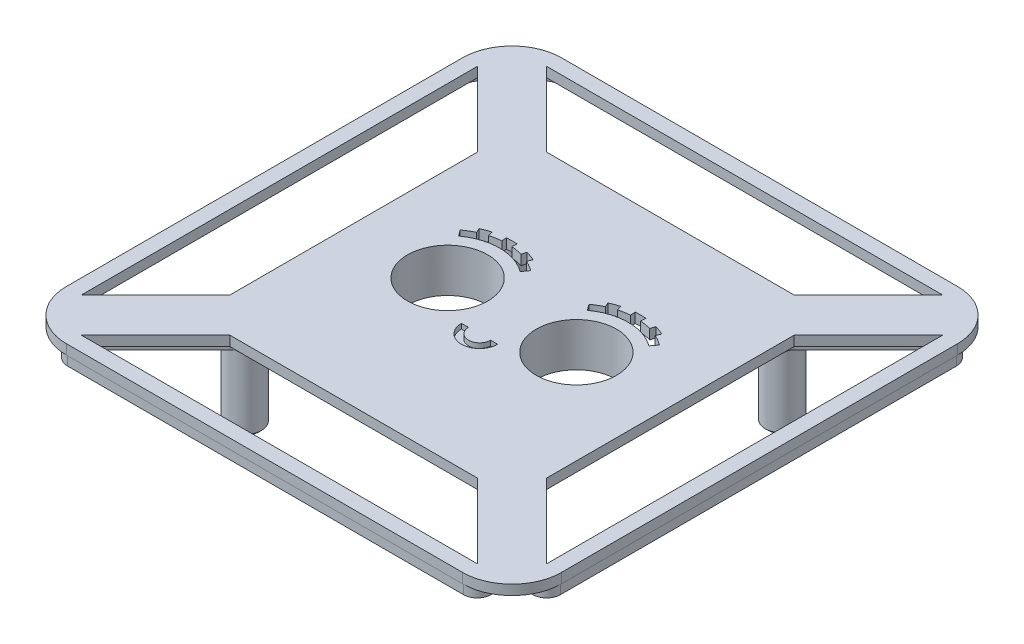
SolidWorks part; units mm, degrees
ref_plane "Front Plane" through (0, 0, 0) normal (0, 0, 1) x (1, 0, 0)
ref_plane "Top Plane" through (0, 0, 0) normal (0, 1, 0) x (1, 0, 0)
ref_plane "Right Plane" through (0, 0, 0) normal (1, 0, 0) x (0, 0, -1)
sketch "Sketch1" plane through (0, 0, 0) normal (0, 1, 0) x (1, 0, 0)
  line L0 (0, 50) -> (3, 50)
  line L1 (10, 0) -> (90, 0)
  line L2 (0, 10) -> (0, 90)
  line L3 (10, 100) -> (90, 100)
  line L4 (100, 10) -> (100, 90)
  line L5 (3, 10) -> (3, 90)
  line L6 (3, 90) -> (18, 75)
  line L7 (18, 75) -> (18, 25)
  line L8 (3, 10) -> (18, 25)
  line L9 (50, 82) -> (50, 18) construction
  line L10 (50, 50) -> (63, 50) construction
  line L11 (97, 10) -> (82, 25)
  line L12 (82, 75) -> (82, 25)
  line L13 (97, 90) -> (82, 75)
  line L14 (97, 10) -> (97, 90)
  line L15 (10, 3) -> (25, 18)
  line L16 (75, 18) -> (25, 18)
  line L17 (90, 3) -> (75, 18)
  line L18 (10, 3) -> (90, 3)
  line L19 (10, 97) -> (90, 97)
  line L20 (90, 97) -> (75, 82)
  line L21 (75, 82) -> (25, 82)
  line L22 (10, 97) -> (25, 82)
  line L24 (30.7834, 58.4364) -> (29.8814, 59.6605)
  line L32 (57.9669, 60.8935) -> (57.5475, 61.8013)
  line L33 (59.7375, 61.548) -> (59.4657, 62.5103)
  line L34 (61.9916, 61.9576) -> (61.9076, 62.954)
  line L35 (64.0084, 61.9576) -> (64.0924, 62.954)
  line L36 (66.2625, 61.548) -> (66.5343, 62.5103)
  line L37 (68.0331, 60.8935) -> (68.4525, 61.8013)
  line L38 (69.2166, 58.4364) -> (70.1186, 59.6605)
  line L39 (56.7834, 58.4364) -> (55.8814, 59.6605)
  line L40 (43.2166, 58.4364) -> (44.1186, 59.6605)
  line L41 (42.0331, 60.8935) -> (42.4525, 61.8013)
  line L42 (40.2625, 61.548) -> (40.5343, 62.5103)
  line L43 (38.0084, 61.9576) -> (38.0924, 62.954)
  line L44 (35.9916, 61.9576) -> (35.9076, 62.954)
  line L45 (33.7375, 61.548) -> (33.4657, 62.5103)
  line L46 (31.9669, 60.8935) -> (31.5475, 61.8013)
  arc A0 (90, 100) -> (100, 90) centre (90, 90) cw
  arc A1 (90, 0) -> (100, 10) centre (90, 10) ccw
  arc A2 (10, 0) -> (0, 10) centre (10, 10) cw
  arc A3 (0, 90) -> (10, 100) centre (10, 90) cw
  circle A4 centre (63, 50) radius 8.1
  circle A5 centre (37, 50) radius 8.1
  arc A6 (69.2166, 58.4364) -> (56.7834, 58.4364) centre (63, 50) ccw
  arc A7 (70.1186, 59.6605) -> (68.0331, 60.8935) centre (63, 50) ccw
  arc A8 (68.4525, 61.8013) -> (66.5343, 62.5103) centre (63, 50) ccw
  arc A9 (59.4657, 62.5103) -> (57.5475, 61.8013) centre (63, 50) ccw
  arc A10 (64.0924, 62.954) -> (61.9076, 62.954) centre (63, 50) ccw
  arc A11 (57.9669, 60.8935) -> (55.8814, 59.6605) centre (63, 50) ccw
  arc A12 (61.9916, 61.9576) -> (59.7375, 61.548) centre (63, 50) ccw
  arc A13 (66.2625, 61.548) -> (64.0084, 61.9576) centre (63, 50) ccw
  arc A14 (30.7834, 58.4364) -> (43.2166, 58.4364) centre (37, 50) cw
  arc A15 (42.0331, 60.8935) -> (44.1186, 59.6605) centre (37, 50) cw
  arc A16 (40.5343, 62.5103) -> (42.4525, 61.8013) centre (37, 50) cw
  arc A17 (38.0084, 61.9576) -> (40.2625, 61.548) centre (37, 50) cw
  arc A18 (35.9076, 62.954) -> (38.0924, 62.954) centre (37, 50) cw
  arc A19 (33.7375, 61.548) -> (35.9916, 61.9576) centre (37, 50) cw
  arc A20 (31.5475, 61.8013) -> (33.4657, 62.5103) centre (37, 50) cw
  arc A21 (29.8814, 59.6605) -> (31.9669, 60.8935) centre (37, 50) cw
  point P9 (100, 0)
  point P12 (0, 0)
  point P15 (0, 100)
  point P24 (18, 50)
  dimension "D3" = 10
  dimension "D6" = 13
  dimension "D7" = 16.2
  dimension "D1" = 100
  dimension "D2" = 100
  dimension "D4" = 135
  dimension "D5" = 15
extrude "Boss-Extrude1" add sketch "Sketch1" along normal blind 2 contours A3 L2 L5 L6 L7 L8 A2 L1 A1 L4 A0 L3 L14 L11 L12 L13 L18 L15 L16 L17 L22 L19 L20 L21 A4 A5 region at (50, 0, -49.8916)
sketch "Sketch3" plane through (0, 0, 0) normal (0, -1, 0) x (1, 0, 0)
  line L0 (3, -10) -> (18, -25) construction
  line L1 (18, -75) -> (18, -25) construction
  line L2 (3, -10) -> (3, -90) construction
  line L3 (3, -90) -> (18, -75) construction
  line L4 (10, -100) -> (90, -100)
  line L5 (100, -90) -> (100, -10)
  line L6 (90, 0) -> (10, 0)
  line L7 (0, -10) -> (0, -90)
  line L8 (10, -100) -> (90, -100)
  line L9 (100, -90) -> (100, -10)
  line L10 (90, 0) -> (10, 0)
  line L11 (0, -10) -> (0, -90)
  line L12 (10, -3) -> (25, -18) construction
  line L13 (75, -18) -> (25, -18) construction
  line L14 (82, -75) -> (82, -25) construction
  line L15 (97, -10) -> (82, -25) construction
  line L16 (97, -10) -> (97, -90) construction
  line L17 (97, -90) -> (82, -75) construction
  line L18 (90, -97) -> (75, -82) construction
  line L19 (75, -82) -> (25, -82) construction
  line L20 (10, -97) -> (25, -82) construction
  line L21 (10, -97) -> (90, -97) construction
  line L22 (10, -3) -> (90, -3) construction
  line L23 (90, -3) -> (75, -18) construction
  line L24 (90, -3) -> (75, -18)
  line L25 (10, -3) -> (90, -3)
  line L26 (10, -97) -> (90, -97)
  line L27 (10, -97) -> (25, -82)
  line L28 (75, -82) -> (25, -82)
  line L29 (90, -97) -> (75, -82)
  line L30 (97, -90) -> (82, -75)
  line L31 (97, -10) -> (97, -90)
  line L32 (97, -10) -> (82, -25)
  line L33 (82, -75) -> (82, -25)
  line L34 (75, -18) -> (25, -18)
  line L35 (10, -3) -> (25, -18)
  line L36 (3, -90) -> (18, -75)
  line L37 (3, -10) -> (3, -90)
  line L38 (18, -75) -> (18, -25)
  line L39 (3, -10) -> (18, -25)
  line L40 (91.4142, -4.4142) -> (76.4142, -19.4142)
  line L41 (75, -20) -> (25, -20)
  line L42 (8.5858, -4.4142) -> (23.5858, -19.4142)
  line L43 (10, -1) -> (90, -1)
  line L44 (4.4142, -91.4142) -> (19.4142, -76.4142)
  line L45 (20, -75) -> (20, -25)
  line L46 (4.4142, -8.5858) -> (19.4142, -23.5858)
  line L47 (1, -10) -> (1, -90)
  line L48 (10, -99) -> (90, -99)
  line L49 (91.4142, -95.5858) -> (76.4142, -80.5858)
  line L50 (75, -80) -> (25, -80)
  line L51 (8.5858, -95.5858) -> (23.5858, -80.5858)
  line L52 (95.5858, -91.4142) -> (80.5858, -76.4142)
  line L53 (80, -75) -> (80, -25)
  line L54 (95.5858, -8.5858) -> (80.5858, -23.5858)
  line L55 (99, -10) -> (99, -90)
  line L56 (94.8284, -1) -> (75.8284, -20) construction
  line L57 (75.8284, -20) -> (24.1716, -20) construction
  line L58 (5.1716, -1) -> (94.8284, -1) construction
  line L59 (5.1716, -1) -> (24.1716, -20) construction
  line L60 (20, -75.8284) -> (20, -24.1716) construction
  line L61 (1, -5.1716) -> (20, -24.1716) construction
  line L62 (1, -5.1716) -> (1, -94.8284) construction
  line L63 (1, -94.8284) -> (20, -75.8284) construction
  line L64 (5.1716, -99) -> (94.8284, -99) construction
  line L65 (5.1716, -99) -> (24.1716, -80) construction
  line L66 (75.8284, -80) -> (24.1716, -80) construction
  line L67 (94.8284, -99) -> (75.8284, -80) construction
  line L68 (99, -94.8284) -> (80, -75.8284) construction
  line L69 (99, -5.1716) -> (99, -94.8284) construction
  line L70 (80, -75.8284) -> (80, -24.1716) construction
  line L71 (99, -5.1716) -> (80, -24.1716) construction
  line L72 (95.0201, -8.0201) -> (80.0201, -23.0201)
  line L73 (79.2, -75) -> (79.2, -25)
  line L74 (95.0201, -91.9799) -> (80.0201, -76.9799)
  line L75 (99.8, -10) -> (99.8, -90)
  line L76 (91.9799, -95.0201) -> (76.9799, -80.0201)
  line L77 (75, -79.2) -> (25, -79.2)
  line L78 (8.0201, -95.0201) -> (23.0201, -80.0201)
  line L79 (10, -99.8) -> (90, -99.8)
  line L80 (0.2, -10) -> (0.2, -90)
  line L81 (4.9799, -8.0201) -> (19.9799, -23.0201)
  line L82 (20.8, -75) -> (20.8, -25)
  line L83 (4.9799, -91.9799) -> (19.9799, -76.9799)
  line L84 (8.0201, -4.9799) -> (23.0201, -19.9799)
  line L85 (10, -0.2) -> (90, -0.2)
  line L86 (91.9799, -4.9799) -> (76.9799, -19.9799)
  line L87 (75, -20.8) -> (25, -20.8)
  circle A0 centre (37, -50) radius 8.1 construction
  circle A1 centre (63, -50) radius 8.1 construction
  circle A2 centre (63, -50) radius 8.1
  circle A3 centre (37, -50) radius 8.1
  arc A4 (0, -90) -> (10, -100) centre (10, -90) ccw
  arc A5 (90, -100) -> (100, -90) centre (90, -90) ccw
  arc A6 (100, -10) -> (90, 0) centre (90, -10) ccw
  arc A7 (10, 0) -> (0, -10) centre (10, -10) ccw
  arc A8 (0, -90) -> (10, -100) centre (10, -90) ccw
  arc A9 (90, -100) -> (100, -90) centre (90, -90) ccw
  arc A10 (100, -10) -> (90, 0) centre (90, -10) ccw
  arc A11 (10, 0) -> (0, -10) centre (10, -10) ccw
  arc A12 (76.4142, -19.4142) -> (75, -20) centre (75, -18) cw
  arc A13 (91.4142, -4.4142) -> (90, -1) centre (90, -3) ccw
  arc A14 (8.5858, -4.4142) -> (10, -1) centre (10, -3) cw
  arc A15 (25, -20) -> (23.5858, -19.4142) centre (25, -18) cw
  arc A16 (20, -25) -> (19.4142, -23.5858) centre (18, -25) ccw
  arc A17 (4.4142, -8.5858) -> (1, -10) centre (3, -10) ccw
  arc A18 (19.4142, -76.4142) -> (20, -75) centre (18, -75) ccw
  arc A19 (4.4142, -91.4142) -> (1, -90) centre (3, -90) cw
  arc A20 (10, -99) -> (8.5858, -95.5858) centre (10, -97) cw
  arc A21 (25, -80) -> (23.5858, -80.5858) centre (25, -82) ccw
  arc A22 (76.4142, -80.5858) -> (75, -80) centre (75, -82) ccw
  arc A23 (90, -99) -> (91.4142, -95.5858) centre (90, -97) ccw
  arc A24 (95.5858, -91.4142) -> (99, -90) centre (97, -90) ccw
  arc A25 (80.5858, -76.4142) -> (80, -75) centre (82, -75) cw
  arc A26 (80, -25) -> (80.5858, -23.5858) centre (82, -25) cw
  arc A27 (95.5858, -8.5858) -> (99, -10) centre (97, -10) cw
  circle A28 centre (63, -50) radius 10.1
  circle A29 centre (37, -50) radius 10.1
  arc A30 (79.2, -25) -> (80.0201, -23.0201) centre (82, -25) cw
  arc A31 (80.0201, -76.9799) -> (79.2, -75) centre (82, -75) cw
  arc A32 (95.0201, -91.9799) -> (99.8, -90) centre (97, -90) ccw
  arc A33 (95.0201, -8.0201) -> (99.8, -10) centre (97, -10) cw
  arc A34 (90, -99.8) -> (91.9799, -95.0201) centre (90, -97) ccw
  arc A35 (76.9799, -80.0201) -> (75, -79.2) centre (75, -82) ccw
  arc A36 (25, -79.2) -> (23.0201, -80.0201) centre (25, -82) ccw
  arc A37 (10, -99.8) -> (8.0201, -95.0201) centre (10, -97) cw
  arc A38 (4.9799, -91.9799) -> (0.2, -90) centre (3, -90) cw
  arc A39 (4.9799, -8.0201) -> (0.2, -10) centre (3, -10) ccw
  arc A40 (20.8, -25) -> (19.9799, -23.0201) centre (18, -25) ccw
  arc A41 (19.9799, -76.9799) -> (20.8, -75) centre (18, -75) ccw
  arc A42 (25, -20.8) -> (23.0201, -19.9799) centre (25, -18) cw
  arc A43 (8.0201, -4.9799) -> (10, -0.2) centre (10, -3) cw
  arc A44 (91.9799, -4.9799) -> (90, -0.2) centre (90, -3) ccw
  arc A45 (76.9799, -19.9799) -> (75, -20.8) centre (75, -18) cw
  dimension "D3" = 2
  dimension "D1" = 0
  dimension "D2" = 2
  dimension "D4" = 2
  dimension "D5" = 0.8
extrude "Boss-Extrude2" add sketch "Sketch3" along normal blind 2 contours A45 L86 A44 L85 A43 L84 A42 L87 L41 A15 L42 A14 L43 A13 L40 A12 | L83 A41 L82 A40 L81 A39 L80 A38 L44 A19 L47 A17 L46 A16 L45 A18 | A33 L72 A30 L73 A31 L74 A32 L75 L54 A27 L55 A24 L52 A25 L53 A26 | A37 L79 A34 L76 A35 L77 A36 L78 A23 L48 A20 L51 A21 L50 A22 L49 region at (98.0378, 0, -7.4945) region at (92.5055, 0, -98.0378) region at (1.9622, 0, -7.4945) region at (7.4945, 0, -1.9622)
extrude "Boss-Extrude3" add sketch "Sketch3<4>" along normal blind 6.8 contours A29 L61 | A28 L60 region at (53.1857, 0, -50) region at (27.1857, 0, -50)
sketch "Sketch3<4>" plane through (0, 0, 0) normal (0, -1, 0) x (1, 0, 0) same geometry as "Sketch3"
sketch "Sketch4" plane through (0, 2, 0) normal (0, 1, 0) x (1, 0, 0)
  line L0 (37, 50) -> (63, 50) construction
  line L1 (50, 50) -> (50, 45.6888) construction
  line L2 (46.341, 43.4527) -> (47.7639, 43.4527)
  line L3 (52.2361, 43.4527) -> (53.659, 43.4527)
  arc A0 (47.7639, 43.4527) -> (52.2361, 43.4527) centre (50, 43.4527) ccw
  arc A1 (46.341, 43.4527) -> (53.659, 43.4527) centre (50, 43.4527) ccw
extrude "Cut-Extrude1" cut sketch "Sketch4" against normal blind 1
chamfer "Chamfer1" distance 1 angle 45 2 edges at (37, -6.8, -60.1) (63, -6.8, -60.1)
sketch "Sketch5" plane through (0, 0, 0) normal (0, -1, 0) x (1, 0, 0)
  line L0 (50, 0) -> (23, 0) construction
  line L1 (10, 0) -> (90, 0) construction
  line L2 (23, 0) -> (23, -23) construction
  circle A0 centre (23, -23) radius 1.5
  circle A1 centre (23, -23) radius 3.3852
  dimension "D1" = 27
  dimension "D2" = 23
extrude "Boss-Extrude4" add sketch "Sketch5" along normal blind 17 contours A1 | A0
ref_plane "Plane1" through (50, 0, 0) normal (1, 0, 0) x (0, 0, -1)
mirror "Mirror1" about plane through (50, 0, 0) normal (1, 0, 0) of "Boss-Extrude4"
ref_plane "Plane2" through (0, 0, -50.2864) normal (0, 0, 1) x (1, 0, 0)
mirror "Mirror2" about plane through (0, 0, -50.2864) normal (0, 0, 1) of "Mirror1"
chamfer "Chamfer2" distance 0.5 angle 45 8 edges at (23, -17, -24.5) (23, -17, -26.3852) (23, -17, -74.1876) (23, -17, -76.0728) (77, -17, -76.0728) (77, -17, -74.1876) (77, -17, -24.5) (77, -17, -26.3852)
